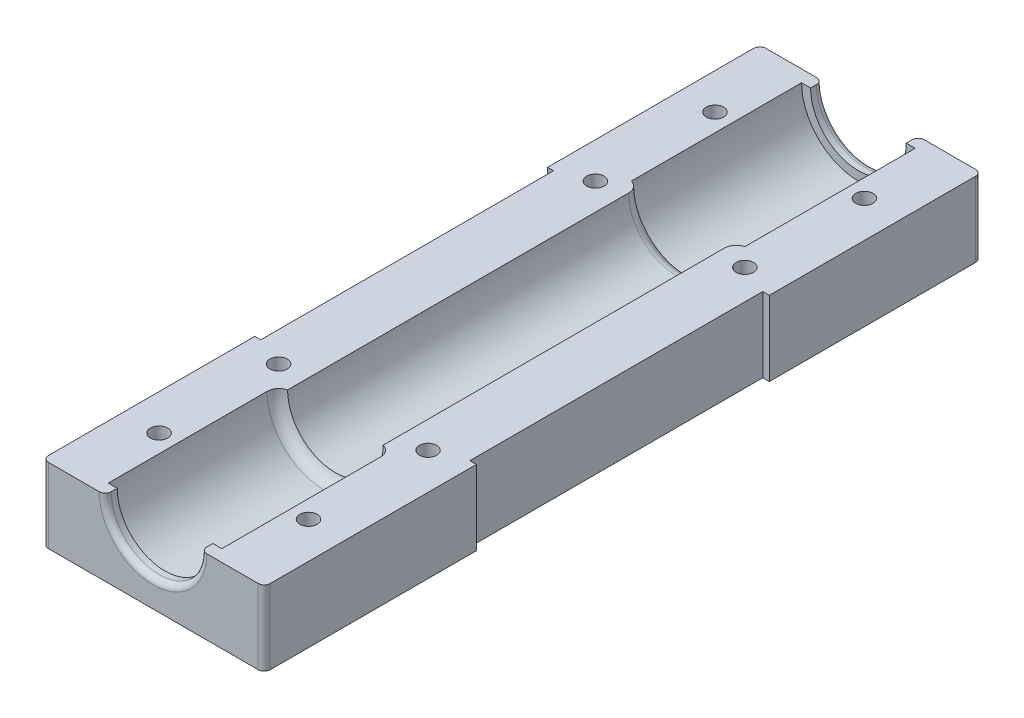
SolidWorks part; units mm, degrees
ref_plane "Front Plane" through (0, 0, 0) normal (0, 0, 1) x (1, 0, 0)
ref_plane "Top Plane" through (0, 0, 0) normal (0, 1, 0) x (1, 0, 0)
ref_plane "Right Plane" through (0, 0, 0) normal (1, 0, 0) x (0, 0, -1)
sketch "Sketch2" plane through (0, 0, 0) normal (0, 0, 1) x (1, 0, 0)
  line L1 (-12.5, -12.5) -> (12.5, -12.5)
  line L2 (-12.5, -12.5) -> (-12.5, 6)
  line L4 (12.5, -12.5) -> (12.5, 6)
  line L5 (-12.5, -12.5) -> (5.6569, 5.6569) construction
  line L8 (-12.5, 6) -> (-12.5, 12.9518)
  line L9 (0, 9) -> (0, 0) construction
  line L12 (12.5, 6) -> (12.5, 12.9518)
  line L14 (-1, 16.9722) -> (-5.9954, 16.9722)
  line L15 (-1, 16.9722) -> (5.9954, 16.9722)
  line L17 (-5.6569, 5.6569) -> (12.5, -12.5) construction
  circle A0 centre (0, 0) radius 8
  arc A1 (12.5, 12.9518) -> (5.9954, 16.9722) centre (0, 0) ccw
  arc A3 (-5.9954, 16.9722) -> (-12.5, 12.9518) centre (0, 0) ccw
  point P0 (0, 0)
  dimension "D3" = 36
  dimension "D1" = 25
extrude "Boss-Extrude1" add sketch "Sketch2" along normal blind 41 and the other way blind 18
sketch "Sketch3" plane through (0, 0, 41) normal (0, 0, 1) x (1, 0, 0)
  line L0 (-1, 17.975) -> (0.7273, 17.975)
  line L2 (-13.5, 6.2234) -> (-13.5, 14.7564)
  line L8 (-13.5, 6.2234) -> (-13.5, -12.5)
  line L9 (13.596, -12.5) -> (-13.5, -12.5)
  line L10 (13.596, 6.2249) -> (13.596, 14.668)
  line L13 (-1, 17.975) -> (-8.7693, 17.975)
  line L14 (0.7273, 17.975) -> (8.7693, 17.975)
  line L15 (13.596, -12.5) -> (13.596, 6.2249)
  arc A0 (13.596, 14.668) -> (8.7693, 17.975) centre (0, 0) ccw
  arc A1 (-8.7693, 17.975) -> (-13.5, 14.7564) centre (0, 0) ccw
  circle A2 centre (0, 0) radius 9.5
  point P20 (-1, 19.975)
  dimension "D1" = 40
  dimension "D2" = 2
extrude "Boss-Extrude2" add sketch "Sketch3" along normal blind 28.5
ref_plane "Plane2" through (0, 0, 11.5) normal (0, 0, 1) x (1, 0, 0)
mirror "Mirror1" about plane through (0, 0, 11.5) normal (0, 0, 1) of "Boss-Extrude2"
sketch "Sketch4" plane through (0, -12.5, 0) normal (0, -1, 0) x (1, 0, 0)
  line L0 (-13.5, 69.5) -> (13.596, 69.5) construction
  line L1 (-13.5, 69.5) -> (13.596, 69.5)
  line L2 (-18.5, 42.75) -> (-18.5, 69.5)
  line L4 (18.596, 42.75) -> (18.596, 69.5)
  line L5 (-13.5, 69.5) -> (-18.5, 69.5)
  line L6 (13.596, 69.5) -> (18.596, 69.5)
  line L8 (-17.5, -13) -> (-18.5, -13)
  line L9 (-17.5, -13) -> (-18.5, -13)
  line L13 (-18.5, -46.5) -> (18.596, -46.5)
  line L21 (-18.5, -13) -> (-18.5, -51.5)
  line L22 (-18.5, -13) -> (-18.5, -51.5)
  line L23 (-18.5, -51.5) -> (18.596, -51.5)
  line L24 (17.5, -13) -> (17.5, 36)
  line L25 (17.5, 36) -> (18.596, 36)
  line L26 (18.596, 36) -> (18.596, 74.5)
  line L27 (18.596, 74.5) -> (-18.5, 74.5)
  line L28 (-18.5, 74.5) -> (-18.5, 36)
  line L29 (-18.5, 36) -> (-17.5, 36)
  line L30 (-17.5, 36) -> (-17.5, -13)
  line L31 (18.596, -51.5) -> (18.596, -13)
  line L32 (18.596, -51.5) -> (18.596, -13)
  line L33 (18.596, -13) -> (17.5, -13)
  line L34 (18.596, -13) -> (17.5, -13)
  line L36 (17.5, -13) -> (17.5, 36)
  line L37 (17.5, 36) -> (18.596, 36)
  line L38 (18.596, 36) -> (18.596, 42.75)
  line L40 (-18.5, 42.75) -> (-18.5, 36)
  line L41 (-18.5, 36) -> (-17.5, 36)
  line L42 (-17.5, 36) -> (-17.5, -13)
  line M13 (12.5, -18) -> (12.5, 41)
  line M14 (12.5, 41) -> (13.596, 41)
  line M15 (13.596, 41) -> (13.596, 69.5)
  line M16 (13.596, 69.5) -> (-13.5, 69.5)
  line M17 (-13.5, 69.5) -> (-13.5, 41)
  line M18 (-13.5, 41) -> (-12.5, 41)
  line M19 (-12.5, 41) -> (-12.5, -18)
  line M20 (-12.5, -18) -> (-13.5, -18)
  line M21 (-13.5, -18) -> (-13.5, -46.5)
  line M22 (-13.5, -46.5) -> (13.596, -46.5)
  line M23 (13.596, -46.5) -> (13.596, -18)
  line M24 (13.596, -18) -> (12.5, -18)
  dimension "D1" = 5
extrude "Boss-Extrude3" add sketch "Sketch4" along normal blind 5 contours L41 L42 L9 L22 L13 L5 L2 L40 M21 M20 M19 M18 M17 | L37 L38 L4 L6 L13 L32 L34 L36 M15 M14 M13 M24 M23 | M24 M13 M14 M15 M16 M17 M18 M19 M20 M21 M22 M23 region at (-15.5339, -12.5, 11.5) region at (0.0245, -12.5, 11.5) region at (15.5851, -12.5, 11.5)
sketch "Sketch5" plane through (0, -12.5, 0) normal (0, 1, 0) x (1, 0, 0)
  line L1 (13.596, -41) -> (13.596, -69.5) construction
  line L12 (13.596, -69.5) -> (18.596, -69.5) construction
  line L24 (18.596, -69.5) -> (18.596, -36) construction
  line L25 (18.596, -36) -> (17.5, -36) construction
  line L26 (17.5, -36) -> (17.5, 13) construction
  line L27 (17.5, 13) -> (18.596, 13) construction
  line L28 (18.596, 13) -> (18.596, 46.5) construction
  line L29 (18.596, 46.5) -> (13.596, 46.5) construction
  line L30 (13.596, 46.5) -> (13.596, 18) construction
  line L31 (13.596, 18) -> (12.5, 18) construction
  line L32 (12.5, 18) -> (12.5, -41) construction
  line L33 (12.5, -41) -> (13.596, -41) construction
  line L34 (-18.5, -69.5) -> (-13.5, -69.5) construction
  line L35 (-13.5, -69.5) -> (-13.5, -41) construction
  line L36 (-13.5, -41) -> (-12.5, -41) construction
  line L37 (-12.5, -41) -> (-12.5, 18) construction
  line L38 (-12.5, 18) -> (-13.5, 18) construction
  line L39 (-13.5, 18) -> (-13.5, 46.5) construction
  line L40 (-13.5, 46.5) -> (-18.5, 46.5) construction
  line L41 (-18.5, 46.5) -> (-18.5, 13) construction
  line L42 (-18.5, 13) -> (-17.5, 13) construction
  line L43 (-17.5, 13) -> (-17.5, -36) construction
  line L44 (-17.5, -36) -> (-18.5, -36) construction
  line L45 (-18.5, -36) -> (-18.5, -69.5) construction
  line L46 (13.596, -41) -> (13.596, -69.5)
  line L47 (13.596, -69.5) -> (18.596, -69.5)
  line L48 (18.596, -69.5) -> (18.596, -36)
  line L49 (18.596, -36) -> (17.5, -36)
  line L50 (17.5, -36) -> (17.5, 13)
  line L51 (17.5, 13) -> (18.596, 13)
  line L52 (18.596, 13) -> (18.596, 46.5)
  line L53 (18.596, 46.5) -> (13.596, 46.5)
  line L54 (13.596, 46.5) -> (13.596, 18)
  line L55 (13.596, 18) -> (12.5, 18)
  line L56 (12.5, 18) -> (12.5, -41)
  line L57 (12.5, -41) -> (13.596, -41)
  line L58 (-18.5, -69.5) -> (-13.5, -69.5)
  line L59 (-13.5, -69.5) -> (-13.5, -41)
  line L60 (-13.5, -41) -> (-12.5, -41)
  line L61 (-12.5, -41) -> (-12.5, 18)
  line L62 (-12.5, 18) -> (-13.5, 18)
  line L63 (-13.5, 18) -> (-13.5, 46.5)
  line L64 (-13.5, 46.5) -> (-18.5, 46.5)
  line L65 (-18.5, 46.5) -> (-18.5, 13)
  line L66 (-18.5, 13) -> (-17.5, 13)
  line L67 (-17.5, 13) -> (-17.5, -36)
  line L68 (-17.5, -36) -> (-18.5, -36)
  line L69 (-18.5, -36) -> (-18.5, -69.5)
extrude "Boss-Extrude4" add sketch "Sketch5" along normal up to vertex (25.4518 mm away) up to point (-12.5, 12.9518, 41)
sketch "Sketch6" plane through (0, 17.975, 0) normal (0, -1, 0) x (1, 0, 0)
  line L1 (-13.5, -46.5) -> (-18.5, -46.5) construction
  point P0 (-12.5, -15)
  point P1 (12.5, -15)
  point P2 (12.5, -35)
  point P8 (-12.5, -35)
  dimension "D1" = 20
  dimension "D2" = 25
  dimension "D3" = 20
  dimension "D4" = 11.5
  dimension "D6" = 25
hole_wizard "M3.5 Tapped Hole1" positions "Sketch10" profile "Sketch12" tap size "M3.5" standard "ISO" end condition through all
sketch "Sketch10" plane through (0, 16.9722, 0) normal (0, 1, 0) x (1, 0, 0)
  point P0 (-12.5, 15)
  point P6 (12.5, 15)
  point P9 (12.5, 35)
  point P12 (-12.5, 35)
  dimension "D1" = 25
  dimension "D2" = 25
  dimension "D3" = 20
sketch "Sketch12" plane through (-12.5, 16.9722, -15) normal (1, 0, 0) x (0, 0, 1)
  line L0 (0, 0) -> (0, 34.4722)
  line L1 (0, 34.4722) -> (1.45, 34.4722)
  line L2 (1.45, 34.4722) -> (1.45, 0)
  line L5 (1.45, 0) -> (0, 0)
  line L11 (0, -6.35) -> (0, 107.95) construction
  dimension "Thru Tap Drill Dia." = 2.9
  dimension "Thru Tap Drill Depth" = 34.4722
cosmetic thread "Hole Thread13" parameters "D2"=3.5
cosmetic thread "Hole Thread14" parameters "D2"=3.5
cosmetic thread "Hole Thread16" parameters "D2"=3.5
cosmetic thread "Hole Thread17" parameters "D2"=3.5
fillet "Fillet2" radius 2 2 edges at (18.596, 12.9518, -29.75) (-18.5, 12.9518, -29.75)
sketch "Sketch14" plane through (0, 0, 69.5) normal (0, 0, 1) x (1, 0, 0)
  line L0 (-13.5, 12.9518) -> (13.596, 12.9518)
  line L5 (18.596, -17.5) -> (18.596, 10.9518)
  line L6 (18.596, -17.5) -> (18.596, 10.9518)
  line L11 (-18.5, 10.9518) -> (-18.5, -17.5)
  line L12 (13.596, 12.9518) -> (13.596, 14.668)
  line L13 (-18.5, 10.9518) -> (-18.5, -17.5)
  line L14 (8.7693, 17.975) -> (-8.7693, 17.975)
  line L15 (16.596, 12.9518) -> (13.596, 12.9518)
  line L16 (-13.5, 14.7564) -> (-13.5, 12.9518)
  line L17 (16.596, 12.9518) -> (13.596, 12.9518)
  line L18 (-18.5, -17.5) -> (18.596, -17.5)
  line L19 (-18.5, -17.5) -> (18.596, -17.5)
  line L20 (-13.5, 12.9518) -> (-16.5, 12.9518)
  line L21 (-13.5, 12.9518) -> (-16.5, 12.9518)
  circle A0 centre (0, 0) radius 8
  arc A5 (18.596, 10.9518) -> (16.596, 12.9518) centre (16.596, 10.9518) ccw
  arc A6 (18.596, 10.9518) -> (16.596, 12.9518) centre (16.596, 10.9518) ccw
  arc A7 (13.596, 14.668) -> (8.7693, 17.975) centre (0, 0) ccw
  arc A8 (-16.5, 12.9518) -> (-18.5, 10.9518) centre (-16.5, 10.9518) ccw
  arc A9 (-8.7693, 17.975) -> (-13.5, 14.7564) centre (0, 0) ccw
  arc A10 (-16.5, 12.9518) -> (-18.5, 10.9518) centre (-16.5, 10.9518) ccw
  line M45 (18.596, -17.5) -> (18.596, 10.9518)
  line M55 (-18.5, 10.9518) -> (-18.5, -17.5)
  circle M57 centre (0, 0) radius 9.5
  dimension "D1" = 0
extrude "Boss-Extrude5" add sketch "Sketch14" along normal blind 2 contours A0 | L0 M55 M45 M57 region at (0.048, 12.4719, 69.5) region at (-9.2313, 0, 69.5)
fillet "Fillet10" radius 1 7 edges at (18.596, -3.2741, 71.5) (-18.5, -3.2741, 71.5) (8, 0, 71.5) (0.048, -17.5, 71.5) (0.048, 12.9518, 71.5) (18.0102, 12.366, 71.5) (-17.9142, 12.366, 71.5)
mirror "Mirror2" about plane through (0, 0, 11.5) normal (0, 0, 1) of "Fillet10", "Boss-Extrude5"
fillet "Fillet11" radius 1 6 edges at (11.3042, 16.4989, -46.5) (0, 17.975, -46.5) (-11.2503, 16.5357, -46.5) (-11.2503, 16.5357, 69.5) (0, 17.975, 69.5) (11.3042, 16.4989, 69.5)
fillet "Fillet12" radius 2 2 edges at (8, 0, -18) (9.5, 0, 41)
mirror "Mirror3" about plane through (0, 0, 11.5) normal (0, 0, 1) of "M3.5 Tapped Hole1"
sketch "Sketch15" plane through (0, 0, 71.5) normal (0, 0, 1) x (1, 0, 0)
  line L1 (-20.8813, 0) -> (23.6966, 0)
  line L5 (-20.8813, 0) -> (26.1643, 0)
  line L6 (-20.8813, 0) -> (-20.8813, 19.1558)
  line L7 (-20.8813, 19.1558) -> (26.1643, 19.1558)
  line L8 (26.1643, 0) -> (26.1643, 19.1558)
extrude "Cut-Extrude2" cut sketch "Sketch15" against normal through all contours L6 L7 L8 L5
sketch "Sketch16" plane through (0, 0, -48.5) normal (0, 0, -1) x (-1, 0, 0)
  line L0 (18.5, -17.5) -> (-18.596, -17.5) construction
  line L1 (-24.7736, -21.5109) -> (25.5483, -21.5109)
  line L2 (-24.7736, -21.5109) -> (-24.7736, -12.5)
  line L3 (-24.7736, -12.5) -> (25.5483, -12.5)
  line L4 (25.5483, -21.5109) -> (25.5483, -12.5)
  dimension "D1" = 5
extrude "Cut-Extrude3" cut sketch "Sketch16" against normal through all
